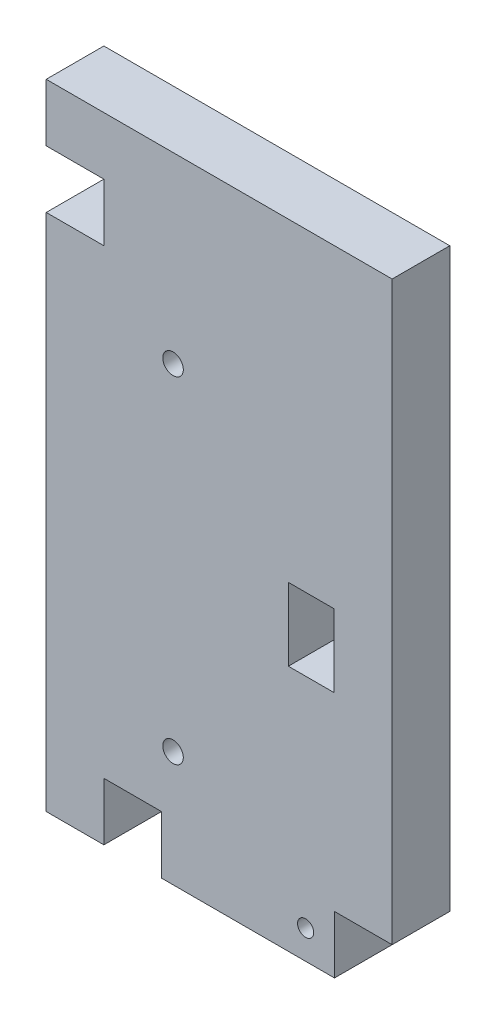
SolidWorks part; units mm, degrees
ref_plane "Front Plane" through (0, 0, 0) normal (0, 0, 1) x (1, 0, 0)
ref_plane "Top Plane" through (0, 0, 0) normal (0, 1, 0) x (1, 0, 0)
ref_plane "Right Plane" through (0, 0, 0) normal (1, 0, 0) x (0, 0, -1)
sketch "Sketch1" plane through (0, 0, 0) normal (0, 0, 1) x (1, 0, 0)
  line L0 (-16.1345, 9.3173) -> (-16.1345, -47.8327)
  line L1 (-16.1345, 22.0173) -> (21.9655, 22.0173)
  line L2 (-16.1345, 22.0173) -> (-16.1345, 15.6673)
  line L3 (-3.4345, -47.8327) -> (15.6155, -47.8327)
  line L4 (21.9655, 22.0173) -> (21.9655, -41.4827)
  line L5 (-16.1345, 15.6673) -> (-9.7845, 15.6673)
  line L7 (-16.1345, 9.3173) -> (-9.7845, 9.3173)
  line L8 (-9.7845, 15.6673) -> (-9.7845, 9.3173)
  line L9 (10.5355, -12.6327) -> (15.5355, -12.6327)
  line L10 (10.5355, -12.6327) -> (10.5355, -20.6327)
  line L11 (10.5355, -20.6327) -> (15.5355, -20.6327)
  line L12 (15.5355, -12.6327) -> (15.5355, -20.6327)
  line L13 (-9.7845, -47.8327) -> (-9.7845, -41.4827)
  line L14 (-9.7845, -41.4827) -> (-3.4345, -41.4827)
  line L15 (-16.1345, -47.8327) -> (-9.7845, -47.8327)
  line L16 (-3.4345, -47.8327) -> (-3.4345, -41.4827)
  line L19 (21.9655, -41.4827) -> (15.6155, -41.4827)
  line L20 (15.6155, -47.8327) -> (15.6155, -41.4827)
  circle A0 centre (-2.1645, -35.1327) radius 1.1303
  circle A1 centre (-2.1645, 1.8673) radius 1.1303
  circle A2 centre (12.4405, -44.6577) radius 0.889
  dimension "D5" = 2.2606
  dimension "D6" = 2.2606
  dimension "D7" = 37
  dimension "D8" = 12.7
  dimension "D10" = 7.62
  dimension "D11" = 0
  dimension "D12" = 14.5
  dimension "D21" = 3.175
  dimension "D22" = 3.175
  dimension "D23" = 1.778
  dimension "D1" = 6.35
  dimension "D2" = 6.35
  dimension "D3" = 6.35
  dimension "D4" = 57.15
  dimension "D9" = 38.1
  dimension "D13" = 8
  dimension "D14" = 12.7
  dimension "D15" = 5
  dimension "D16" = 6.35
  dimension "D17" = 6.35
  dimension "D18" = 6.35
  dimension "D19" = 6.35
  dimension "D20" = 6.35
extrude "Boss-Extrude1" add sketch "Sketch1" along normal blind 6.35
